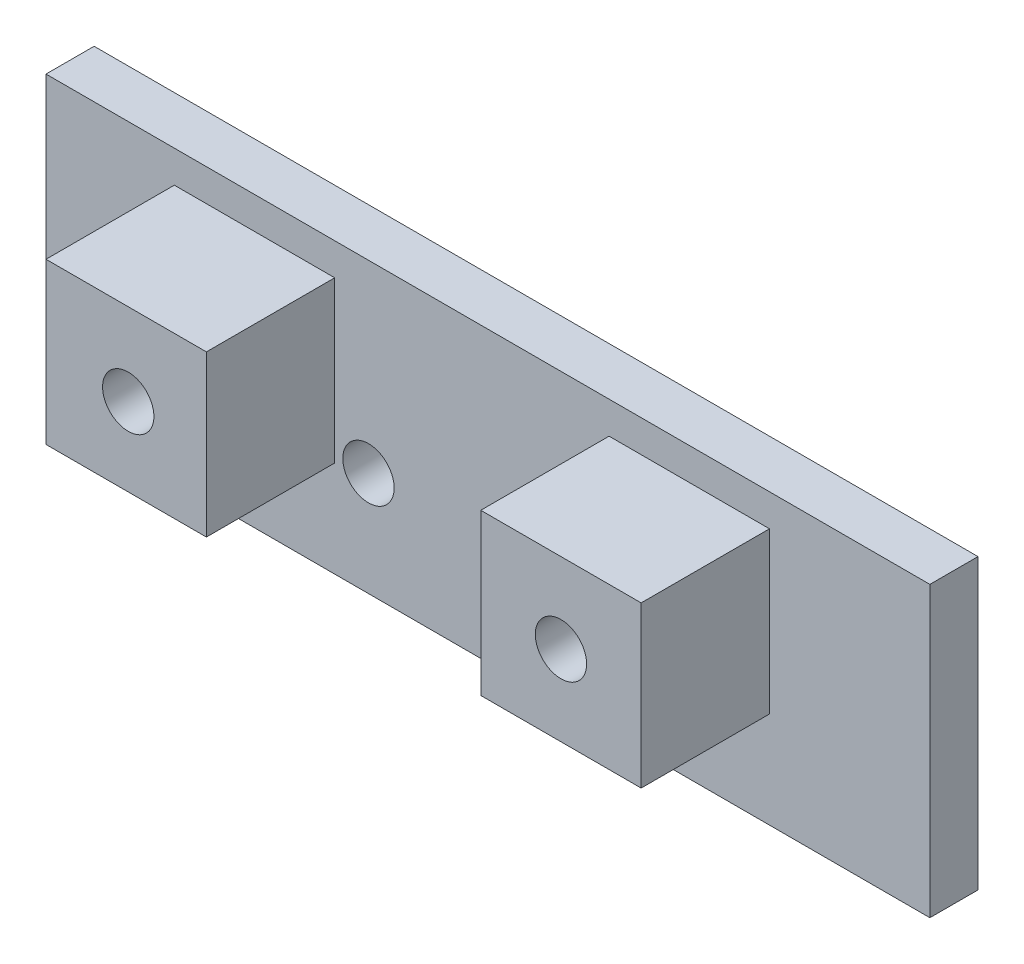
SolidWorks part; units mm, degrees
ref_plane "前视基准面" through (0, 0, 0) normal (0, 0, 1) x (1, 0, 0)
ref_plane "上视基准面" through (0, 0, 0) normal (0, 1, 0) x (1, 0, 0)
ref_plane "右视基准面" through (0, 0, 0) normal (1, 0, 0) x (0, 0, -1)
sketch "草图1" plane through (0, 0, 0) normal (0, 0, 1) x (1, 0, 0)
  line L0 (18.1, 0.8) -> (-9.4526, 0.8)
  line L2 (18.1, 9.8) -> (18.1, 0.8)
  line L3 (-9.4526, 0.8) -> (-9.4526, 9.8)
  line L5 (-9.4526, 9.8) -> (18.1, 9.8)
  circle A1 centre (0.6, 3.3) radius 1.75 construction
  circle A2 centre (0.6, 4.05) radius 1 construction
  dimension "D1" = 2
  dimension "D2" = 9
extrude "base" add sketch "草图1" along normal blind 1.5 contours L5 L2 L0 L3
sketch "草图4" plane through (0, 0, 0) normal (0, 0, -1) x (-1, 0, 0)
  circle A1 centre (-11.1, 3.3) radius 0.85 construction
  circle A3 centre (-0.6, 3.3) radius 1.75 construction
  circle A4 centre (-11.1, 3.3) radius 0.725
  dimension "D1" = 1.45
extrude "axis" add sketch "草图4" along normal offset from surface (1.9 mm away) 0.4 offset beyond the face yes
sketch "草图5" plane through (0, 0, 0) normal (0, 0, -1) x (-1, 0, 0)
  circle A1 centre (-0.6, 3.3) radius 1.75 construction
  circle A2 centre (-0.6, 4.05) radius 1 construction
  dimension "D1" = 2
hole_wizard "M2 螺纹孔的螺纹孔钻头1" positions "3D草图1" profile "草图6" hole size "M2" standard "ISO" end condition up to next
sketch3d "3D草图1"
  point P0 (0.6, 4.05, 0)
sketch "草图6" plane through (0.6, 4.05, 0) normal (1, 0, 0) x (0, 1, 0)
  line L0 (0, 0) -> (0, 1.5)
  line L1 (0, 1.5) -> (0.8, 1.5)
  line L2 (0.8, 1.5) -> (0.8, 0)
  line L5 (0.8, 0) -> (0, 0)
  line L11 (0, -6.35) -> (0, 107.95) construction
  dimension "通孔孔直径" = 1.6
  dimension "通孔孔深度" = 1.5
sketch "草图7" plane through (0, 0, 1.5) normal (0, 0, 1) x (1, 0, 0)
  line L0 (18.1, 9.8) -> (18.1, 0.8) construction
  circle A0 centre (15.1, 4.05) radius 1
  dimension "D1" = 2
  dimension "D2" = 3
sketch "Sketch1" plane through (0, 0, 1.5) normal (0, 0, 1) x (1, 0, 0)
  line L0 (-9.4526, 6.3) -> (18.1, 6.3) construction
  line L1 (-9.4526, 0.8) -> (-9.4526, 9.8) construction
  line L2 (18.1, 9.8) -> (18.1, 0.8) construction
  line L3 (-5.4526, 6.3) -> (-0.4526, 6.3)
  line L4 (8.1, 6.3) -> (13.1, 6.3)
  line L5 (18.1, 0.8) -> (-9.4526, 0.8) construction
  point P10 (0, 0)
  point P11 (0, 0)
  dimension "D1" = 5
  dimension "D2" = 4
  dimension "D3" = 5
  dimension "D4" = 5.5
extrude "拉伸-薄壁1" add sketch "Sketch1" along normal blind 4 thin thin type mid plane wall 5
sketch "草图8" plane through (0, 0, 5.5) normal (0, 0, 1) x (1, 0, 0)
  line L0 (8.1, 8.8) -> (13.1, 3.8) construction
  line L1 (13.1, 3.8) -> (13.1, 8.8) construction
  line L2 (13.1, 8.8) -> (8.1, 3.8) construction
  line L3 (-0.4526, 8.8) -> (-5.4526, 3.8) construction
  line L5 (-5.4526, 8.8) -> (-0.4526, 3.8) construction
  circle A0 centre (10.6, 6.3) radius 0.899 construction
  circle A1 centre (-2.889, 6.2364) radius 0.66 construction
hole_wizard "M2 螺纹孔的螺纹孔钻头2" positions "草图9" profile "草图10" hole size "M2" standard "GB" end condition up to next
sketch "草图9" plane through (0, 0, 5.5) normal (0, 0, 1) x (1, 0, 0)
  point P0 (-2.889, 6.2364)
  point P3 (10.6, 6.3)
sketch "草图10" plane through (-2.889, 6.2364, 5.5) normal (1, 0, 0) x (0, -1, 0)
  line L0 (0, 0) -> (0, 5.5)
  line L1 (0, 5.5) -> (0.8, 5.5)
  line L2 (0.8, 5.5) -> (0.8, 0)
  line L5 (0.8, 0) -> (0, 0)
  line L11 (0, -6.35) -> (0, 107.95) construction
  dimension "通孔孔直径" = 1.6
  dimension "通孔孔深度" = 5.5
